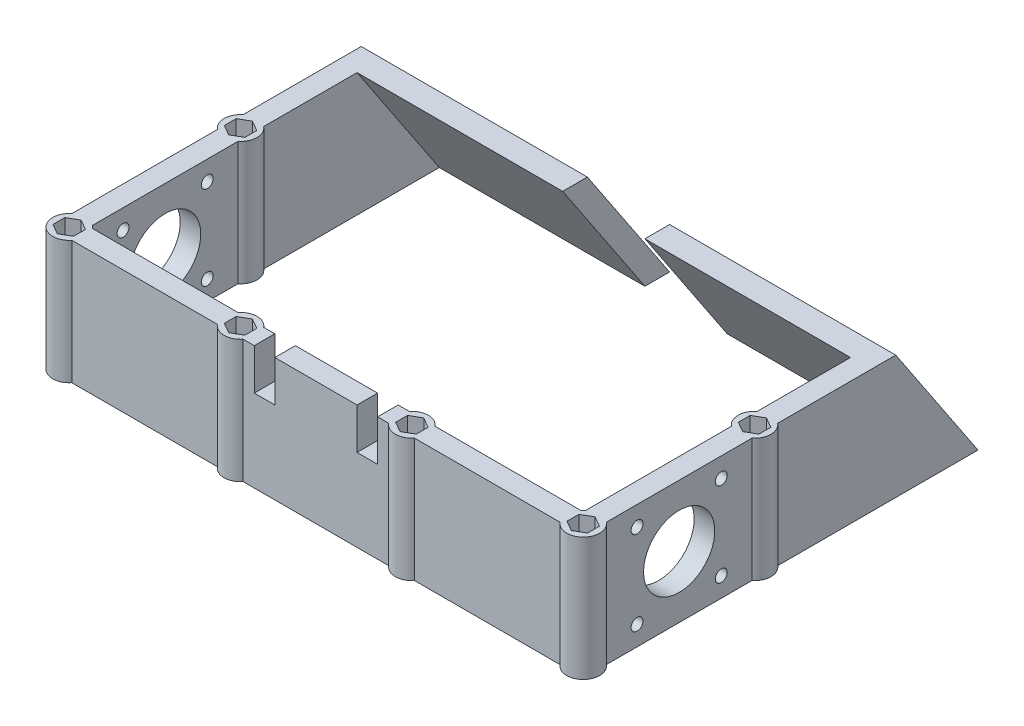
SolidWorks part; units mm, degrees
material "Custom Plastic"
ref_plane "Front Plane" through (0, 0, 0) normal (0, 0, 1) x (1, 0, 0)
ref_plane "Top Plane" through (0, 0, 0) normal (0, 1, 0) x (1, 0, 0)
ref_plane "Right Plane" through (0, 0, 0) normal (1, 0, 0) x (0, 0, -1)
sketch "Sketch4" plane through (0, 0, 0) normal (0, 1, 0) x (1, 0, 0)
  line L0 (0, 0) -> (0, -54.2428)
  line L1 (0, -114.3) -> (52.1261, -114.3) construction
  line L2 (165.1, -107.1594) -> (165.1, -62.1739)
  line L3 (165.1, 0) -> (158.75, 0)
  line L4 (158.75, 0) -> (158.75, -54.2428)
  line L7 (6.35, 0) -> (0, 0)
  line L8 (3.175, -111.125) -> (56.0917, -111.125) construction
  line L9 (56.0917, -111.125) -> (109.0083, -111.125) construction
  line L10 (109.0083, -111.125) -> (161.925, -111.125) construction
  line L11 (161.925, -111.125) -> (161.925, -58.2083) construction
  line L12 (6.35, -107.1594) -> (6.35, -62.1739)
  line L13 (6.35, -54.2428) -> (6.35, 0)
  line L14 (0, -62.1739) -> (0, -114.3) construction
  line L15 (0, -62.1739) -> (0, -107.1594)
  line L16 (7.1406, -114.3) -> (52.1261, -114.3)
  line L17 (52.1261, -107.95) -> (7.1406, -107.95)
  line L18 (60.0572, -114.3) -> (105.0428, -114.3) construction
  line L19 (60.0572, -114.3) -> (105.0428, -114.3)
  line L20 (105.0428, -107.95) -> (60.0572, -107.95)
  line L21 (112.9739, -114.3) -> (165.1, -114.3) construction
  line L22 (112.9739, -114.3) -> (157.9594, -114.3)
  line L23 (158.75, -62.1739) -> (158.75, -107.1594)
  line L24 (165.1, -54.2428) -> (165.1, 0)
  line L26 (157.9594, -107.95) -> (112.9739, -107.95)
  line L27 (0, -56.3752) -> (0, -60.0414)
  line L28 (0, -60.0414) -> (3.175, -61.8745)
  line L29 (3.175, -61.8745) -> (6.35, -60.0414)
  line L30 (6.35, -60.0414) -> (6.35, -56.3752)
  line L31 (6.35, -56.3752) -> (3.175, -54.5422)
  line L32 (3.175, -54.5422) -> (0, -56.3752)
  line L33 (3.175, -107.4588) -> (0, -109.2919)
  line L34 (0, -109.2919) -> (0, -112.9581)
  line L35 (0, -112.9581) -> (3.175, -114.7912)
  line L36 (3.175, -114.7912) -> (6.35, -112.9581)
  line L37 (6.35, -112.9581) -> (6.35, -109.2919)
  line L38 (6.35, -109.2919) -> (3.175, -107.4588)
  line L39 (56.0917, -107.4588) -> (52.9167, -109.2919)
  line L40 (52.9167, -109.2919) -> (52.9167, -112.9581)
  line L41 (52.9167, -112.9581) -> (56.0917, -114.7912)
  line L42 (56.0917, -114.7912) -> (59.2667, -112.9581)
  line L43 (59.2667, -112.9581) -> (59.2667, -109.2919)
  line L44 (59.2667, -109.2919) -> (56.0917, -107.4588)
  line L45 (109.0083, -107.4588) -> (105.8333, -109.2919)
  line L46 (105.8333, -109.2919) -> (105.8333, -112.9581)
  line L47 (105.8333, -112.9581) -> (109.0083, -114.7912)
  line L48 (109.0083, -114.7912) -> (112.1833, -112.9581)
  line L49 (112.1833, -112.9581) -> (112.1833, -109.2919)
  line L50 (112.1833, -109.2919) -> (109.0083, -107.4588)
  line L51 (161.925, -107.4588) -> (158.75, -109.2919)
  line L52 (158.75, -109.2919) -> (158.75, -112.9581)
  line L53 (158.75, -112.9581) -> (161.925, -114.7912)
  line L54 (161.925, -114.7912) -> (165.1, -112.9581)
  line L55 (165.1, -112.9581) -> (165.1, -109.2919)
  line L56 (165.1, -109.2919) -> (161.925, -107.4588)
  line L57 (161.925, -54.5422) -> (158.75, -56.3752)
  line L58 (158.75, -56.3752) -> (158.75, -60.0414)
  line L59 (158.75, -60.0414) -> (161.925, -61.8745)
  line L60 (161.925, -61.8745) -> (165.1, -60.0414)
  line L61 (165.1, -60.0414) -> (165.1, -56.3752)
  line L62 (165.1, -56.3752) -> (161.925, -54.5422)
  arc A6 (0, -54.2428) -> (0, -62.1739) centre (3.175, -58.2083) ccw
  arc A7 (6.35, -62.1739) -> (6.35, -54.2428) centre (3.175, -58.2083) ccw
  arc A8 (0, -107.1594) -> (7.1406, -114.3) centre (3.175, -111.125) ccw
  arc A9 (60.0572, -107.95) -> (52.1261, -107.95) centre (56.0917, -111.125) ccw
  arc A10 (52.1261, -114.3) -> (60.0572, -114.3) centre (56.0917, -111.125) ccw
  arc A11 (105.0428, -114.3) -> (112.9739, -114.3) centre (109.0083, -111.125) ccw
  arc A12 (112.9739, -107.95) -> (105.0428, -107.95) centre (109.0083, -111.125) ccw
  arc A13 (157.9594, -114.3) -> (165.1, -107.1594) centre (161.925, -111.125) ccw
  arc A14 (158.75, -54.2428) -> (158.75, -62.1739) centre (161.925, -58.2083) ccw
  arc A15 (165.1, -62.1739) -> (165.1, -54.2428) centre (161.925, -58.2083) ccw
  arc A16 (6.35, -107.1594) -> (7.1406, -107.95) centre (3.175, -111.125) cw
  arc A17 (158.75, -107.1594) -> (157.9594, -107.95) centre (161.925, -111.125) ccw
  circle A18 centre (3.175, -58.2083) radius 3.175 construction
  circle A19 centre (3.175, -111.125) radius 3.175 construction
  circle A20 centre (56.0917, -111.125) radius 3.175 construction
  circle A21 centre (109.0083, -111.125) radius 3.175 construction
  circle A22 centre (161.925, -111.125) radius 3.175 construction
  circle A23 centre (161.925, -58.2083) radius 3.175 construction
  point P7 (0, 0)
  point P30 (161.925, 0)
  point P51 (3.175, 0)
  dimension "D6" = 6.35
  dimension "D8" = 5.08
  dimension "D10" = 10.16
  dimension "D11" = 5.08
  dimension "D12" = 5.08
  dimension "D13" = 10.16
  dimension "D14" = 10.16
  dimension "D15" = 6.35
  dimension "D16" = 6.35
  dimension "D17" = 6.35
  dimension "D18" = 6.35
  dimension "D19" = 6.35
  dimension "D2" = 6.35
  dimension "D3" = 6.35
  dimension "D4" = 165.1
  dimension "D5" = 114.3
  dimension "D7" = 3.175
  dimension "D9" = 6.35
extrude "Boss-Extrude2" add sketch "Sketch4" along normal blind 38.1
chamfer "Chamfer2" distance 38.1 distance2 25.4 2 edges at (161.925, 38.1, 0) (3.175, 38.1, 0) first distance on face at (161.925, 19.05, 0) first distance on face at (3.175, 19.05, 0)
sketch "Sketch6" plane through (0, 0, 114.3) normal (0, 0, 1) x (1, 0, 0)
  line L0 (63.5, 38.1) -> (63.5, 25.4)
  line L1 (60.0572, 38.1) -> (105.0428, 38.1) construction
  line L2 (63.5, 25.4) -> (69.85, 25.4)
  line L3 (69.85, 25.4) -> (69.85, 38.1)
  line L4 (95.25, 38.1) -> (95.25, 25.4)
  line L5 (95.25, 25.4) -> (101.6, 25.4)
  line L6 (101.6, 25.4) -> (101.6, 38.1)
  line L7 (95.25, 38.1) -> (101.6, 38.1)
  line L8 (63.5, 38.1) -> (69.85, 38.1)
  line L9 (60.0572, 38.1) -> (63.5, 38.1) construction
  line L10 (101.6, 38.1) -> (105.0428, 38.1) construction
  dimension "D1" = 6.35
  dimension "D2" = 6.35
  dimension "D3" = 12.7
  dimension "D4" = 12.7
  dimension "D5" = 25.4
extrude "Cut-Extrude3" cut sketch "Sketch6" against normal through all
sketch "Sketch7" plane through (165.1, 0, 0) normal (1, 0, 0) x (0, 0, -1)
  line L0 (-71.6667, 32.05) -> (-97.6667, 6.05) construction
  line L1 (-71.6667, 32.05) -> (-71.6667, 6.05) construction
  line L2 (-71.6667, 6.05) -> (-97.6667, 6.05) construction
  line L3 (-97.6667, 6.05) -> (-97.6667, 32.05) construction
  line L4 (-97.6667, 32.05) -> (-71.6667, 32.05) construction
  line L6 (-116.205, 38.1) -> (-116.205, 0) construction
  line L7 (-116.205, 19.05) -> (-84.6667, 19.05) construction
  line L8 (-84.6667, 19.05) -> (-84.6667, 38.1) construction
  line L9 (-107.1594, 38.1) -> (-62.1739, 38.1) construction
  circle A0 centre (-84.6667, 19.05) radius 10.9855
  circle A1 centre (-71.6667, 32.05) radius 1.8415
  circle A2 centre (-71.6667, 6.05) radius 1.8415
  circle A3 centre (-97.6667, 6.05) radius 1.8415
  circle A4 centre (-97.6667, 32.05) radius 1.8415
  dimension "D2" = 21.971
  dimension "D3" = 3.683
  dimension "D1" = 26
extrude "Cut-Extrude4" cut sketch "Sketch7" against normal through all
sketch "Sketch8" plane through (0, 0, 0) normal (0, 0.5547, -0.8321) x (-1, 0, 0)
  line L0 (-165.1, 45.7905) -> (-95.25, 45.7905)
  line L1 (-95.25, 45.7905) -> (-95.25, 0)
  line L2 (-95.25, 0) -> (-165.1, 0)
  line L3 (-165.1, 0) -> (-165.1, 45.7905)
  line L4 (-69.85, 45.7905) -> (0, 45.7905)
  line L5 (0, 45.7905) -> (0, 0)
  line L6 (0, 0) -> (-69.85, 0)
  line L7 (-69.85, 0) -> (-69.85, 45.7905)
  point P3 (-63.2499, 45.1653)
  point P14 (0, 0)
  point P15 (0, 0)
extrude "Boss-Extrude3" add sketch "Sketch8" along normal blind 6.35
sketch "Sketch9" plane through (165.1, 0, 0) normal (1, 0, 0) x (0, 0, -1)
  line L0 (-25.4, 38.1) -> (-17.7682, 38.1)
  line L1 (-20.1165, 41.6223) -> (5.2835, 3.5223) construction
  line L2 (-17.7682, 38.1) -> (-20.1165, 41.6223)
  line L3 (-20.1165, 41.6223) -> (-25.4, 38.1)
extrude "Cut-Extrude5" cut sketch "Sketch9" against normal through all and the other way through all
sketch "Sketch10" plane through (165.1, 0, 0) normal (1, 0, 0) x (0, 0, -1)
  line L0 (0, 0) -> (7.6318, 0)
  line L1 (7.6318, 0) -> (5.2835, 3.5223)
  line L2 (-17.7682, 38.1) -> (5.2835, 3.5223) construction
  line L3 (5.2835, 3.5223) -> (0, 0)
extrude "Boss-Extrude4" add sketch "Sketch10" against normal up to surface (69.85 mm away) up to face at (95.25, 19.9306, 9.4712)
sketch "Sketch11" plane through (0, 0, 0) normal (-1, 0, 0) x (0, 0, 1)
  line L0 (-5.2835, 3.5223) -> (-7.6318, 0)
  line L1 (-7.6318, 0) -> (0, 0)
  line L2 (0, 0) -> (-5.2835, 3.5223)
extrude "Boss-Extrude5" add sketch "Sketch11" against normal up to surface (69.85 mm away) up to face at (69.85, 19.9306, 9.4712)
